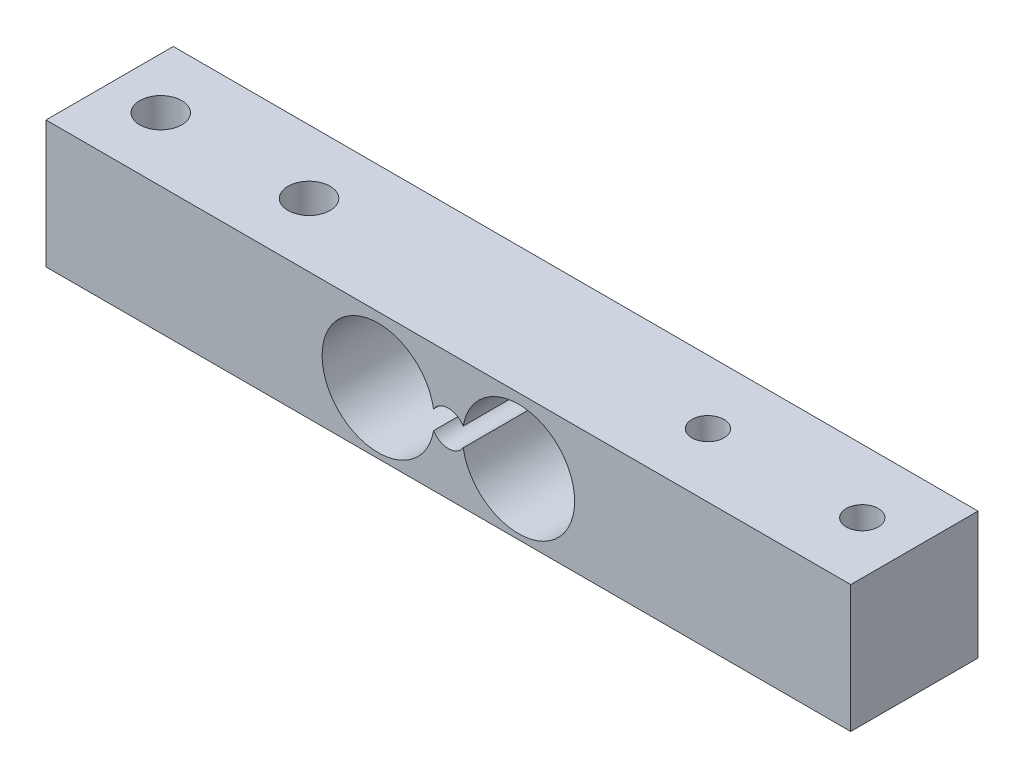
SolidWorks part; units mm, degrees
ref_plane "Plan de face" through (0, 0, 0) normal (0, 0, 1) x (1, 0, 0)
ref_plane "Plan de dessus" through (0, 0, 0) normal (0, 1, 0) x (1, 0, 0)
ref_plane "Plan de droite" through (0, 0, 0) normal (1, 0, 0) x (0, 0, -1)
sketch "Esquisse1" plane through (0, 0, 0) normal (0, 1, 0) x (1, 0, 0)
  line L1 (0, 0) -> (80.3, 0)
  line L2 (0, 0) -> (0, -12.7)
  line L3 (0, -12.7) -> (80.3, -12.7)
  line L4 (80.3, 0) -> (80.3, -12.7)
  dimension "D1" = 80.3
  dimension "D2" = 12.7
extrude "Boss.-Extru.1" add sketch "Esquisse1" along normal blind 12.7
sketch "Esquisse2" plane through (0, 12.7, 0) normal (0, 1, 0) x (1, 0, 0)
  line L0 (0, -6.35) -> (80.3, -6.35) construction
  line L1 (0, 0) -> (0, -12.7) construction
  line L2 (80.3, -12.7) -> (80.3, 0) construction
  circle A0 centre (5.1, -6.35) radius 2.1
  circle A1 centre (19.9, -6.35) radius 2.1
  circle A2 centre (59.7, -6.35) radius 1.6
  circle A3 centre (75.1, -6.35) radius 1.6
  point P14 (0, 0)
  point P15 (0, 0)
  point P16 (0, 0)
  point P17 (0, 0)
  point P18 (0, 0)
  dimension "D1" = 4.2
  dimension "D2" = 4.2
  dimension "D5" = 3.2
  dimension "D6" = 3.2
  dimension "D3" = 14.8
  dimension "D4" = 5.1
  dimension "D7" = 15.4
  dimension "D8" = 5.2
extrude "Enlèv. mat.-Extru.1" cut sketch "Esquisse2" against normal blind 12.7
sketch "Esquisse3" plane through (0, 0, 12.7) normal (0, 0, 1) x (1, 0, 0)
  line L0 (40.15, 12.7) -> (40.15, 0) construction
  line L1 (0, 12.7) -> (80.3, 12.7) construction
  line L2 (0, 0) -> (80.3, 0) construction
  arc A0 (38.6713, 7.0571) -> (38.6713, 5.1854) centre (33.15, 6.1212) ccw
  arc A1 (41.6287, 7.0571) -> (38.6713, 7.0571) centre (40.15, 6.1212) ccw
  arc A2 (41.6287, 5.1854) -> (41.6287, 7.0571) centre (47.15, 6.1212) ccw
  arc A3 (38.6713, 5.1854) -> (41.6287, 5.1854) centre (40.15, 6.1212) ccw
  point P12 (51.2635, 6.1212)
  point P13 (40.15, 6.1212)
  point P14 (33.3401, 6.1212)
  point P15 (47.1595, 6.1212)
  dimension "D1" = 11.2
  dimension "D2" = 11.2
  dimension "D3" = 3.5
  dimension "D4" = 7
  dimension "D5" = 7
extrude "Enlèv. mat.-Extru.2" cut sketch "Esquisse3" against normal blind 12.7
equation "\"D2@Esquisse2\"=\"D1@Esquisse2\""
equation "\"D3@Esquisse2\"=19-4.2"
equation "\"D4@Esquisse2\"=3+\"D1@Esquisse2\"/2"
equation "\"D7@Esquisse2\"=18.6-\"D5@Esquisse2\""
equation "\"D6@Esquisse2\"=\"D5@Esquisse2\""
equation "\"D8@Esquisse2\"=3.6+\"D5@Esquisse2\"/2"
equation "\"D2@Esquisse3\"=\"D1@Esquisse3\""
equation "\"D5@Esquisse3\"=\"D4@Esquisse3\""
